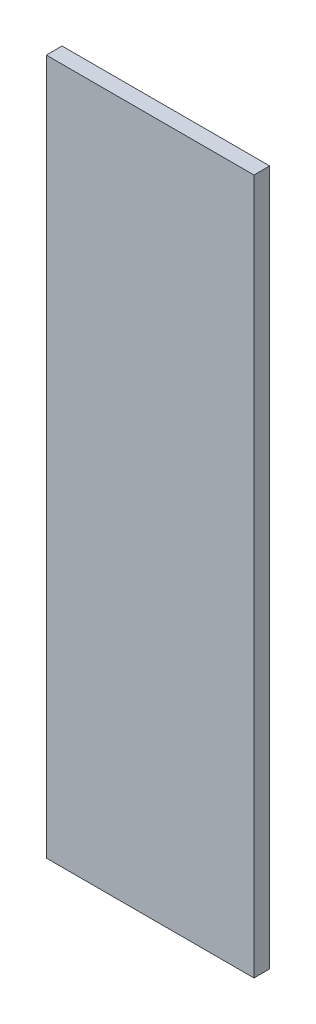
SolidWorks part; units mm, degrees
material "ABS"
ref_plane "Front Plane" through (0, 0, 0) normal (0, 0, 1) x (1, 0, 0)
ref_plane "Top Plane" through (0, 0, 0) normal (0, 1, 0) x (1, 0, 0)
ref_plane "Right Plane" through (0, 0, 0) normal (1, 0, 0) x (0, 0, -1)
sketch "Sketch1" plane through (0, 0, 0) normal (0, 0, 1) x (1, 0, 0)
  line L1 (-66, 221) -> (66, 221)
  line L2 (-66, 221) -> (-66, -221)
  line L3 (-66, -221) -> (66, -221)
  line L4 (66, 221) -> (66, -221)
  line L5 (-66, 221) -> (66, -221) construction
  line L6 (-66, -221) -> (66, 221) construction
  point P0 (0, 0)
  dimension "D1" = 442
  dimension "D2" = 132
extrude "Boss-Extrude1" add sketch "Sketch1" along normal mid plane 10
